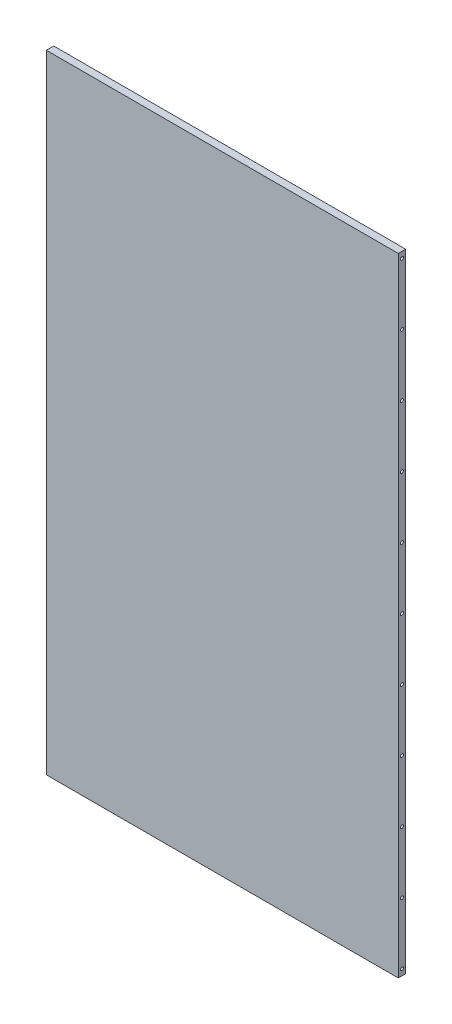
SolidWorks part; units mm, degrees
ref_plane "Front" through (0, 0, 0) normal (0, 0, 1) x (1, 0, 0)
ref_plane "Top" through (0, 0, 0) normal (0, 1, 0) x (1, 0, 0)
ref_plane "Right" through (0, 0, 0) normal (1, 0, 0) x (0, 0, -1)
sketch "Sketch1" plane through (0, 0, 0) normal (0, 0, 1) x (1, 0, 0)
  line L1 (0, 0) -> (286, 0)
  line L2 (0, 0) -> (0, 510)
  line L3 (0, 510) -> (286, 510)
  line L4 (286, 0) -> (286, 510)
  dimension "D1" = 286
  dimension "D2" = 510
extrude "Boss-Extrude1" add sketch "Sketch1" along normal blind 5.9944
hole_wizard "Tap Drill for M3x0.5 Tap1" positions "Sketch3" profile "Sketch2" hole size "M3x0.5" standard "ANSI Metric"
sketch "Sketch3" plane through (286, 0, 0) normal (1, 0, 0) x (0, 0, -1)
  line L0 (-2.9972, 0) -> (-2.9972, 510) construction
  line L1 (-5.9944, 0) -> (0, 0) construction
  line L2 (-5.9944, 510) -> (0, 510) construction
  point P0 (-2.9972, 255)
  point P9 (-1.0578, 246.8367)
  point P10 (-2.9972, 255)
sketch "Sketch2" plane through (286, 255, 2.9972) normal (0, 1, 0) x (0, 0, -1)
  line L0 (0, 0) -> (0, 30.7511)
  line L1 (0, 30.7511) -> (1.25, 30)
  line L2 (1.25, 30) -> (1.25, 0)
  line L5 (1.25, 0) -> (0, 0)
  line L10 (0, 30.7511) -> (-1.25, 30) construction
  line L11 (0, -6.35) -> (0, 107.95) construction
  dimension "Hole Dia." = 2.5
  dimension "Hole Depth" = 30
  dimension "Drill Angle" = 118
pattern_linear "LPattern1" count 6 spacing 50 along (0, 1, 0) count 6 spacing 50 along (0, -1, 0) of "Tap Drill for M3x0.5 Tap1"
ref_plane "Plane1" through (143, 0, 0) normal (1, 0, 0) x (0, 0, -1)
mirror "Mirror1" about plane through (143, 0, 0) normal (1, 0, 0) of "LPattern1", "Tap Drill for M3x0.5 Tap1"
